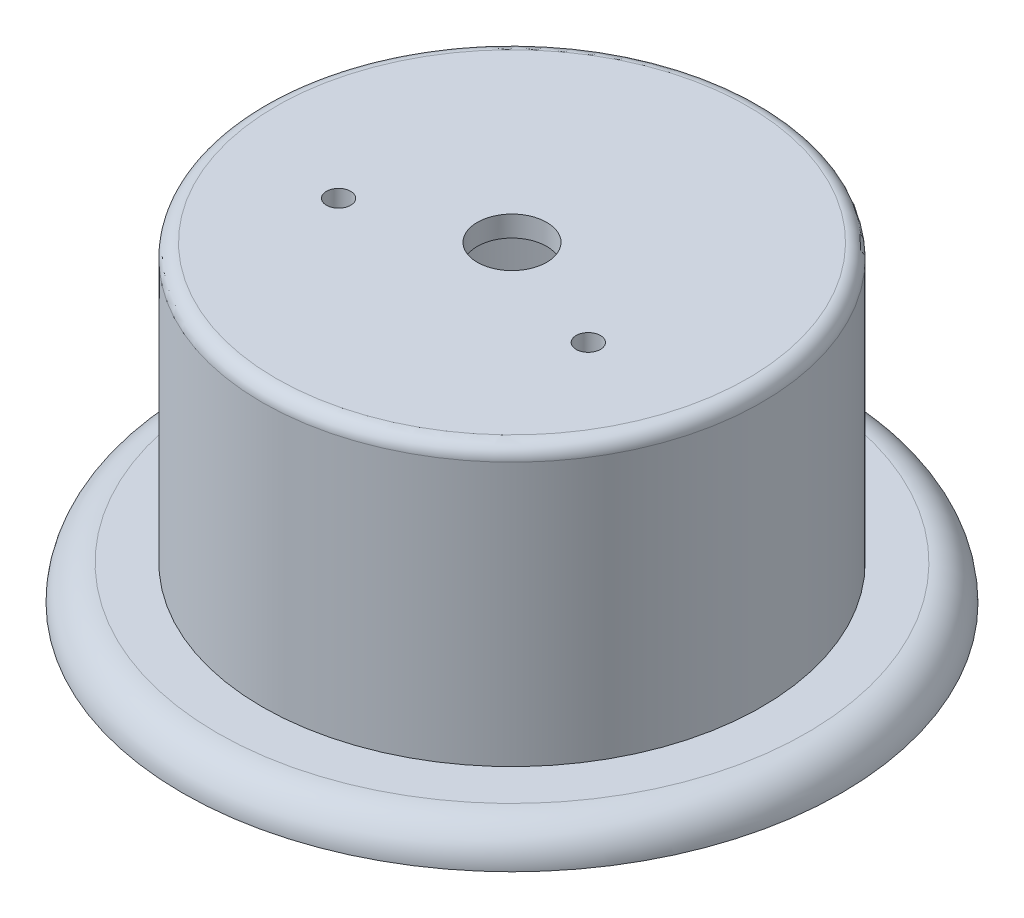
SolidWorks part; units mm, degrees
ref_plane "Front Plane" through (0, 0, 0) normal (0, 0, 1) x (1, 0, 0)
ref_plane "Top Plane" through (0, 0, 0) normal (0, 1, 0) x (1, 0, 0)
ref_plane "Right Plane" through (0, 0, 0) normal (1, 0, 0) x (0, 0, -1)
sketch "Sketch1" plane through (0, 0, 0) normal (0, 1, 0) x (1, 0, 0)
  circle A0 centre (0, 0) radius 47.5
  dimension "D1" = 95
extrude "Boss-Extrude1" add sketch "Sketch1" along normal blind 5
sketch "Sketch2" plane through (0, 5, 0) normal (0, 1, 0) x (1, 0, 0)
  circle A0 centre (0, 0) radius 36
  dimension "D1" = 72
extrude "Boss-Extrude2" add sketch "Sketch2" along normal blind 40
sketch "Sketch3" plane through (0, 0, 0) normal (0, -1, 0) x (1, 0, 0)
  circle A0 centre (0, 0) radius 34.5
  dimension "D1" = 69
extrude "Cut-Extrude1" cut sketch "Sketch3" against normal blind 42
sketch "Sketch4" plane through (0, 45, 0) normal (0, 1, 0) x (1, 0, 0)
  circle A0 centre (0, 0) radius 5
  dimension "D1" = 10
extrude "Cut-Extrude2" cut sketch "Sketch4" against normal blind 5
fillet "Fillet1" radius 5 1 edges at (0, 5, 47.5)
sketch "Sketch5" plane through (0, 45, 0) normal (0, 1, 0) x (1, 0, 0)
  circle A0 centre (18, -7) radius 1.75
  circle A1 centre (-18, -7) radius 1.75
  dimension "D2" = 3.5
  dimension "D5" = 3.5
  dimension "D1" = 7
  dimension "D3" = 18
  dimension "D4" = 7
  dimension "D6" = 18
extrude "Cut-Extrude3" cut sketch "Sketch5" against normal blind 5
fillet "Fillet2" radius 2 1 edges at (0, 45, 36)
